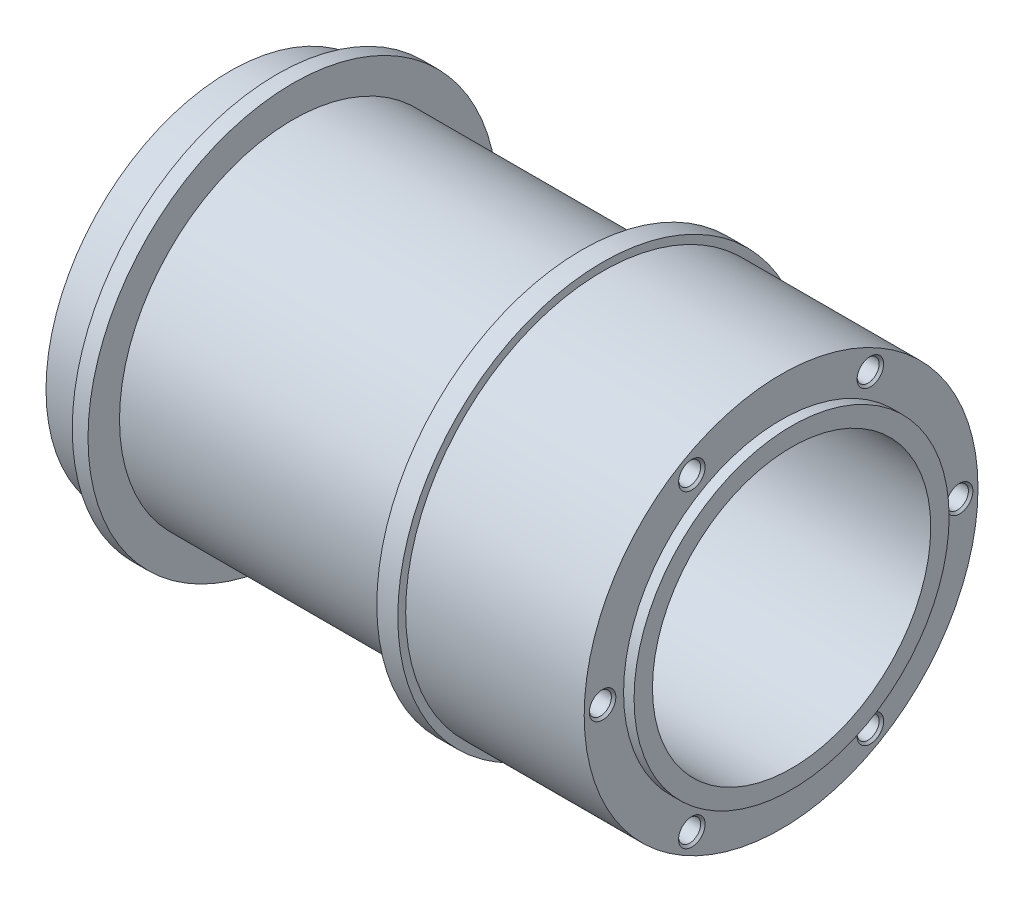
SolidWorks part; units mm, degrees
material "Stop 1060"
ref_plane "Płaszczyzna przednia" through (0, 0, 0) normal (0, 0, 1) x (1, 0, 0)
ref_plane "Płaszczyzna górna" through (0, 0, 0) normal (0, 1, 0) x (1, 0, 0)
ref_plane "Płaszczyzna prawa" through (0, 0, 0) normal (1, 0, 0) x (0, 0, -1)
sketch "Szkic1" plane through (0, 0, 0) normal (0, 0, 1) x (1, 0, 0)
  line L1 (0, 0) -> (47.1008, 0) construction
  line L36 (9, 35) -> (0, 35)
  line L37 (9, 39) -> (9, 35)
  line L38 (71, 37.5) -> (105, 37.5)
  line L39 (71, 39) -> (71, 37.5)
  line L40 (105, 37.5) -> (105, 30)
  line L41 (0, 26.5) -> (107, 26.5)
  line L42 (71, 39) -> (67, 39)
  line L43 (12, 33) -> (67, 33)
  line L44 (12, 39) -> (12, 33)
  line L45 (12, 39) -> (9, 39)
  line L46 (67, 33) -> (67, 39)
  line L47 (107, 30) -> (107, 26.5)
  line L48 (105, 30) -> (107, 30)
  line L49 (0, 26.5) -> (0, 35)
revolve "Obrót1" add sketch "Szkic1" angle 360 about L1
hole_wizard "Otwór gwintowany M51" positions "Szkic2" profile "Szkic4" tap size "M5" standard "DIN"
sketch "Szkic2" plane through (0, 0, 0) normal (-1, 0, 0) x (0, 0, 1)
  point P0 (0, 30)
  point P8 (30, 0)
  point P9 (0, -30)
  point P10 (-30, 0)
  dimension "D1" = 30
  dimension "D2" = 4
cosmetic thread "Gwint otworu1"
cosmetic thread "Gwint otworu2"
cosmetic thread "Gwint otworu3"
cosmetic thread "Gwint otworu4"
sketch "Szkic4" plane through (0, 30, 0) normal (0, 1, 0) x (0, 0, 1)
  line L0 (0, 0) -> (0, 15.2618)
  line L1 (0, 15.2618) -> (2.1, 14)
  line L2 (2.1, 14) -> (2.1, 0.425)
  line L3 (2.1, 0.425) -> (2.525, 0)
  line L5 (2.525, 0) -> (0, 0)
  line L6 (-2.1, 0.425) -> (-2.525, 0) construction
  line L10 (0, 15.2618) -> (-2.1, 14) construction
  line L11 (0, -6.35) -> (0, 107.95) construction
  dimension "Średnica wiertła gwintu" = 4.2
  dimension "Głębokość otworu gwintowanego" = 14
  dimension "Średnica zewnętrznego pogłębienia stożkowego" = 5.05
  dimension "Kąt zewnętrznego pogłębienia stożkowego" = 90
  dimension "Kąt wiertła" = 118
hole_wizard "Otwór gwintowany M52" positions "Szkic5" profile "Szkic6" tap size "M5" standard "DIN"
sketch "Szkic5" plane through (105, 0, 0) normal (1, 0, 0) x (0, 0, -1)
  point P16 (17, 29.4449)
  point P18 (34, 0)
  point P20 (17, -29.4449)
  point P21 (0, 0)
  point P24 (-17, -29.4449)
  point P26 (-34, 0)
  point P28 (-17, 29.4449)
sketch "Szkic6" plane through (105, 29.4449, -17) normal (0, 1, 0) x (0, 0, -1)
  line L0 (0, 0) -> (0, 15.2618)
  line L1 (0, 15.2618) -> (2.1, 14)
  line L2 (2.1, 14) -> (2.1, 0.425)
  line L3 (2.1, 0.425) -> (2.525, 0)
  line L5 (2.525, 0) -> (0, 0)
  line L6 (-2.1, 0.425) -> (-2.525, 0) construction
  line L10 (0, 15.2618) -> (-2.1, 14) construction
  line L11 (0, -6.35) -> (0, 107.95) construction
  dimension "Średnica wiertła gwintu" = 4.2
  dimension "Głębokość otworu gwintowanego" = 14
  dimension "Średnica zewnętrznego pogłębienia stożkowego" = 5.05
  dimension "Kąt zewnętrznego pogłębienia stożkowego" = 90
  dimension "Kąt wiertła" = 118
cosmetic thread "Gwint otworu5"
cosmetic thread "Gwint otworu6"
cosmetic thread "Gwint otworu7"
cosmetic thread "Gwint otworu8"
cosmetic thread "Gwint otworu9"
cosmetic thread "Gwint otworu10"
